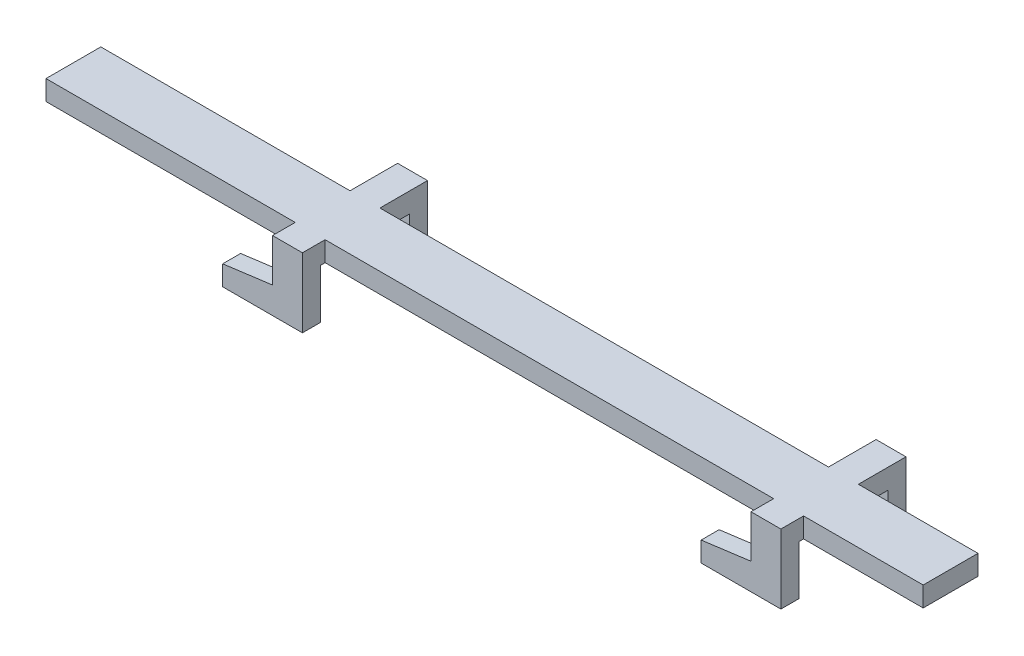
SolidWorks part; units mm, degrees
ref_plane "Top" through (0, 0, 0) normal (0, 0, 1) x (1, 0, 0)
ref_plane "Front" through (0, 0, 0) normal (0, 1, 0) x (1, 0, 0)
ref_plane "Right" through (0, 0, 0) normal (1, 0, 0) x (0, 0, -1)
sketch "Top Sketch" plane through (0, 0, 0) normal (0, 1, 0) x (1, 0, 0)
  line L0 (-12, -5.5) -> (-12, -6.875)
  line L1 (-88, 0) -> (-63, 0)
  line L2 (-88, 0) -> (-88, -5.5)
  line L3 (-88, -5.5) -> (-63, -5.5)
  line L4 (0, 0) -> (0, -5.5)
  line L5 (-12, -6.875) -> (-20, -6.875) construction
  line L6 (-20, -6.875) -> (-20, -5.5) construction
  line L7 (-60, -5.5) -> (-60, -6.875)
  line L8 (-60, -6.875) -> (-68, -6.875) construction
  line L9 (-68, -6.875) -> (-68, -5.5) construction
  line L10 (-12, 0) -> (-12, 3.875)
  line L11 (-12, 3.875) -> (-20, 3.875) construction
  line L12 (-20, 3.875) -> (-20, 0) construction
  line L13 (-60, 0) -> (-60, 3.875)
  line L14 (-60, 3.875) -> (-68, 3.875) construction
  line L15 (-68, 3.875) -> (-68, 0) construction
  line L16 (-12, 0) -> (0, 0)
  line L17 (-12, -5.5) -> (0, -5.5)
  line L18 (-60, 0) -> (-15, 0)
  line L19 (-60, -5.5) -> (-15, -5.5)
  line L20 (-15, 3.875) -> (-15, 0)
  line L21 (-15, 3.875) -> (-12, 3.875)
  line L22 (-15, -5.5) -> (-15, -6.875)
  line L23 (-15, -6.875) -> (-12, -6.875)
  line L24 (-63, 3.875) -> (-63, 0)
  line L25 (-63, 3.875) -> (-60, 3.875)
  line L26 (-63, -6.875) -> (-63, -5.5)
  line L27 (-63, -6.875) -> (-60, -6.875)
  line L28 (-88, -15.863) -> (0, -15.863) construction
  point P28 (0, 0)
  point P31 (0, 0)
  point P32 (-44, -15.863)
  dimension "D1" = 5.5
  dimension "D2" = 88
  dimension "D3" = 1.375
  dimension "D4" = 24
  dimension "D5" = 5
  dimension "D6" = 3.875
  dimension "D7" = 48
  dimension "D8" = 3
extrude "Thickness Extrude" add sketch "Top Sketch" along normal blind 2
sketch "Hook Sketch" plane through (0, 0, 6.875) normal (0, 0, 1) x (1, 0, 0)
  line L0 (-15, 2) -> (-12, 2)
  line L1 (-15, 0) -> (-12, 0) construction
  line L2 (-12, 2) -> (-12, -4.9583)
  line L3 (-12, -4.9583) -> (-20, -4.9583)
  line L4 (-20, -4.9583) -> (-20, -2.9583)
  line L5 (-20, -2.9583) -> (-15, -2.3)
  line L6 (-15, -2.3) -> (-15, 2)
  dimension "D1" = 7.5
  dimension "D2" = 5
  dimension "D3" = 2.3
  dimension "D4" = 2
extrude "Hook 1 Extrude" add sketch "Hook Sketch" against normal blind 0.9 and the other way blind 0.9 separate body
extrude "Hook 2 Extrude" add sketch "Hook Sketch<2>" along normal blind 0.9 and the other way blind 0.9 from surface separate body starting at face at (-13.5, 1, -3.875)
sketch "Hook Sketch<2>" plane through (0, 0, 6.875) normal (0, 0, 1) x (1, 0, 0) same geometry as "Hook Sketch"
pattern_linear "Hook Pattern" count 2 spacing 48 along (-1, 0, 0) of "Hook 1 Extrude", "Hook 2 Extrude"
combine bodies "Combine Bodies" operation type add bodies to combine 101 103 104 105 106
